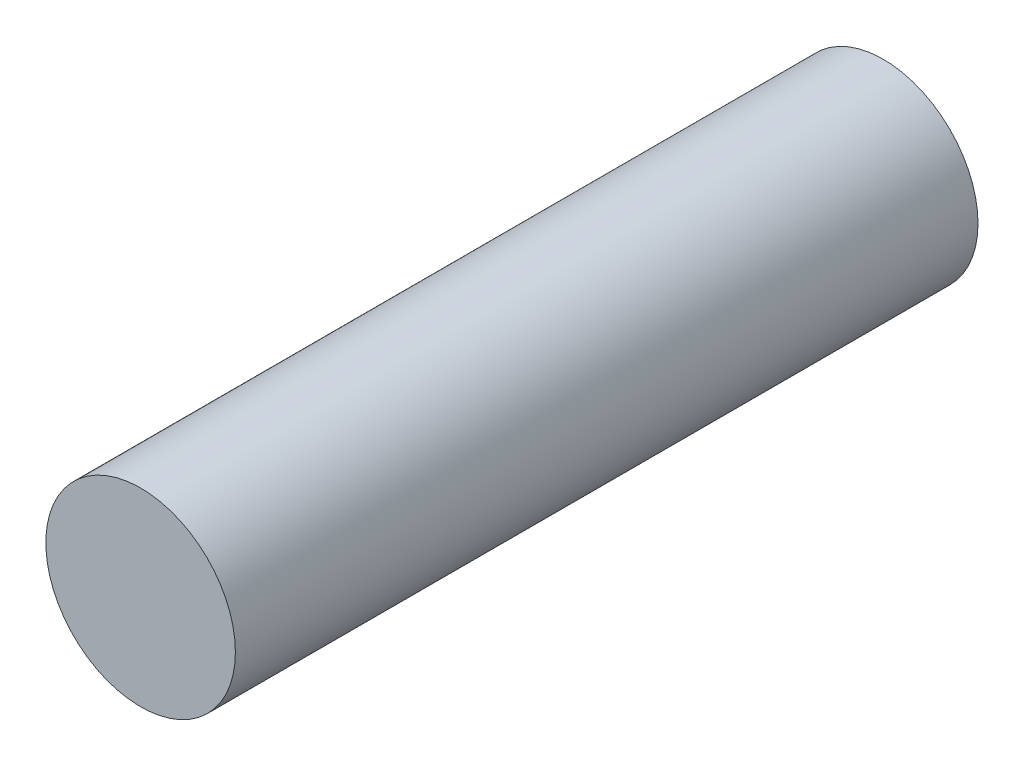
SolidWorks part; units mm, degrees
ref_plane "Front Plane" through (0, 0, 0) normal (0, 0, 1) x (1, 0, 0)
ref_plane "Top Plane" through (0, 0, 0) normal (0, 1, 0) x (1, 0, 0)
ref_plane "Right Plane" through (0, 0, 0) normal (1, 0, 0) x (0, 0, -1)
sketch "Sketch1" plane through (0, 0, 0) normal (0, 0, 1) x (1, 0, 0)
  circle A0 centre (0, 0) radius 2.5
  dimension "D1" = 5
extrude "Boss-Extrude1" add sketch "Sketch1" along normal blind 19.59
equation "\"LA_width\"= 19.59"
equation "\"D1@Boss-Extrude1\"=\"LA_width\""
